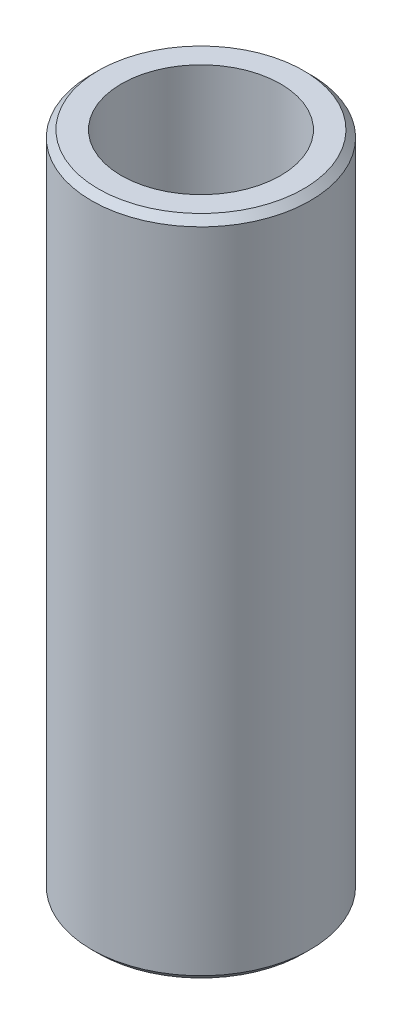
SolidWorks part; units mm, degrees
ref_plane "Front Plane" through (0, 0, 0) normal (0, 0, 1) x (1, 0, 0)
ref_plane "Top Plane" through (0, 0, 0) normal (0, 1, 0) x (1, 0, 0)
ref_plane "Right Plane" through (0, 0, 0) normal (1, 0, 0) x (0, 0, -1)
sketch "Sketch1" plane through (0, 0, 0) normal (0, 1, 0) x (1, 0, 0)
  circle A0 centre (0, 0) radius 47.5
  dimension "SHAFT_OD" = 95
extrude "Boss-Extrude1" add sketch "Sketch1" along normal blind 287.5775
sketch "Sketch2" plane through (0, 0, 0) normal (0, 1, 0) x (1, 0, 0)
  circle A0 centre (0, 0) radius 34.5573
  dimension "BORE_D" = 69.1146
extrude "Cut-Extrude1" cut sketch "Sketch2" along normal through all
chamfer "Chamfer1" distance 2.9566 angle 45 2 edges at (0, 287.5775, 47.5) (0, 0, 47.5)
